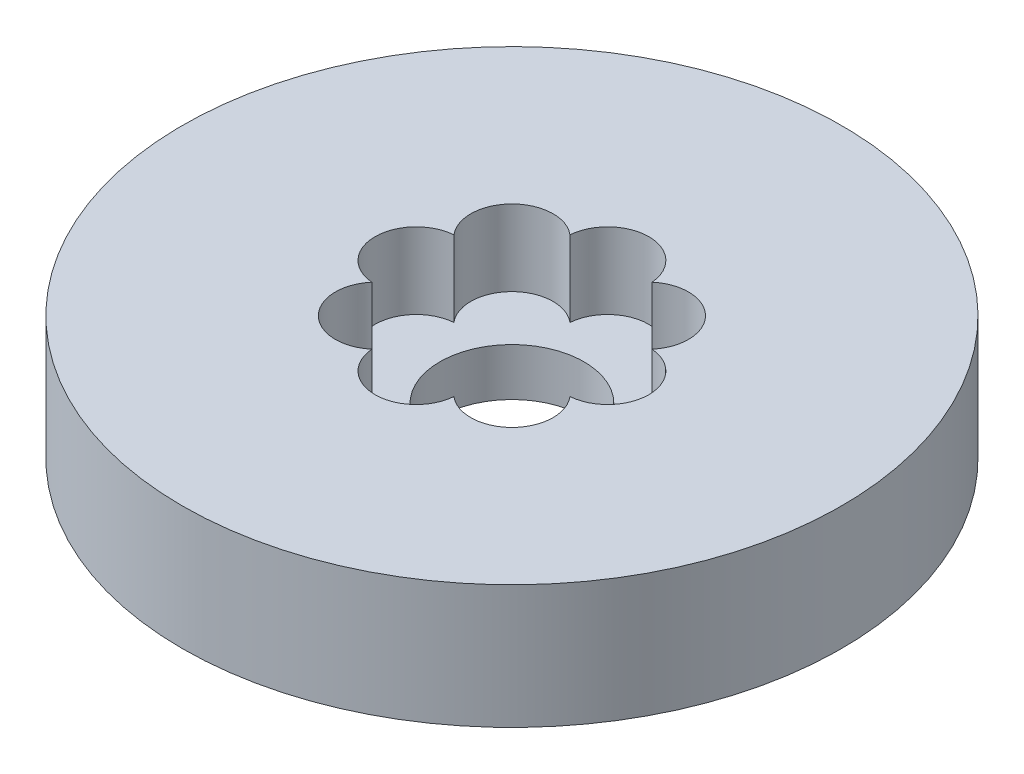
SolidWorks part; units mm, degrees
ref_plane "Front Plane" through (0, 0, 0) normal (0, 0, 1) x (1, 0, 0)
ref_plane "Top Plane" through (0, 0, 0) normal (0, 1, 0) x (1, 0, 0)
ref_plane "Right Plane" through (0, 0, 0) normal (1, 0, 0) x (0, 0, -1)
sketch "Sketch1" plane through (0, 0, 0) normal (0, 1, 0) x (1, 0, 0)
  circle A0 centre (0, 0) radius 80
  dimension "FLANGE_OD" = 160
extrude "Boss-Extrude1" add sketch "Sketch1" along normal blind 30
sketch "Sketch2" plane through (0, 0, 0) normal (0, 1, 0) x (1, 0, 0)
  circle A0 centre (0, 0) radius 17.5
  dimension "BORE_D" = 35
extrude "Cut-Extrude1" cut sketch "Sketch2" along normal through all
sketch "Sketch3" plane through (0, 30, 0) normal (0, 1, 0) x (1, 0, 0)
  circle A0 centre (0, 0) radius 23.2302 construction
  circle A1 centre (-23.2302, 0) radius 10
  dimension "BOLT_D" = 20
  dimension "BOLT_PCD" = 46.4603
extrude "Cut-Extrude2" cut sketch "Sketch3" against normal blind 18.432
pattern_circular "CirPattern1" count 8 over 360 about axis through (0, 0, 0) along (0, 1, 0) of "Cut-Extrude2"
